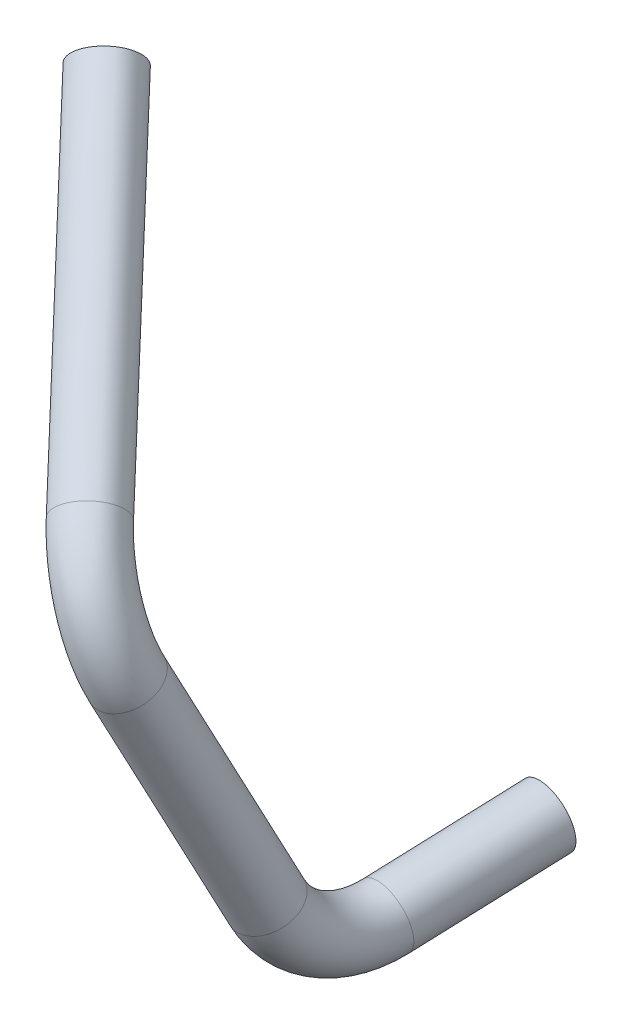
SolidWorks part; units mm, degrees
ref_plane "Piano frontale" through (0, 0, 0) normal (0, 0, 1) x (1, 0, 0)
ref_plane "Piano superiore" through (0, 0, 0) normal (0, 1, 0) x (1, 0, 0)
ref_plane "Piano destro" through (0, 0, 0) normal (1, 0, 0) x (0, 0, -1)
sketch3d "Schizzo3D1"
  line L0 (116.408, -1.8844, -10.3091) -> (125.3523, -9.5492, -0.639)
  line L1 (148.6933, -59.6686, -9.4769) -> (148.404, -60.0583, -7.0488)
  line L2 (125.3523, -9.5492, -0.639) -> (137.7418, -20.1663, 12.756)
  line L3 (143.2114, -30.8925, 14.4066) -> (146.5759, -54.521, 3.3996)
  line L4 (150.1771, -57.6699, -21.9305) -> (148.6933, -59.6686, -9.4769)
  arc A0 (151.3762, -58.7099, -21.9546) -> (148.978, -56.6299, -21.9065) centre (150.1771, -57.6699, -21.9305) ccw construction
  arc A4 (118.197, -0.3189, -10.723) -> (114.6191, -3.45, -9.8953) centre (116.408, -1.8844, -10.3091) ccw construction
  arc A5 (118.197, -0.3189, -10.723) -> (114.6191, -3.45, -9.8953) centre (116.408, -1.8844, -10.3091) ccw construction
  arc A6 (122.9983, -11.609, -0.0945) -> (127.7062, -7.4893, -1.1835) centre (125.3523, -9.5492, -0.639) ccw construction
  arc A7 (122.9983, -11.609, -0.0945) -> (127.7062, -7.4893, -1.1835) centre (125.3523, -9.5492, -0.639) ccw construction
  arc A8 (148.404, -60.0583, -7.0488) -> (146.5759, -54.521, 3.3996) centre (147.4151, -50.2153, -5.5869) ccw
  arc A9 (137.7418, -20.1663, 12.756) -> (143.2114, -30.8925, 14.4066) centre (137.4777, -28.1178, 6.6977) ccw
  point P4 (147.5317, -61.2333, 0.2727)
  point P5 (137.533, -51.0142, -6.8925)
  point P12 (117.8242, -3.098, -8.778)
  point P13 (117.8242, -3.098, -8.778)
  point P17 (123.4889, -7.9523, -2.6536)
  point P19 (123.4889, -7.9523, -2.6536)
  point P23 (150.3626, -57.4201, -23.4872)
  point P25 (142.232, -24.0142, 17.6107)
  point P26 (145.5701, -24.7298, 1.8982)
  point P27 (217.7669, -147.2512, -121.8238)
  point P28 (148.2505, -60.265, -5.7607)
  point P29 (144.204, -32.1133, 15.2183)
  point P30 (200.872, -121.7597, -98.8822)
  dimension "D1" = 10
sweep "Sweep-Sottile1" add path "Schizzo3D1" circular profile diameter 6.35 parameters "D1"=1, "D3"=6.35
